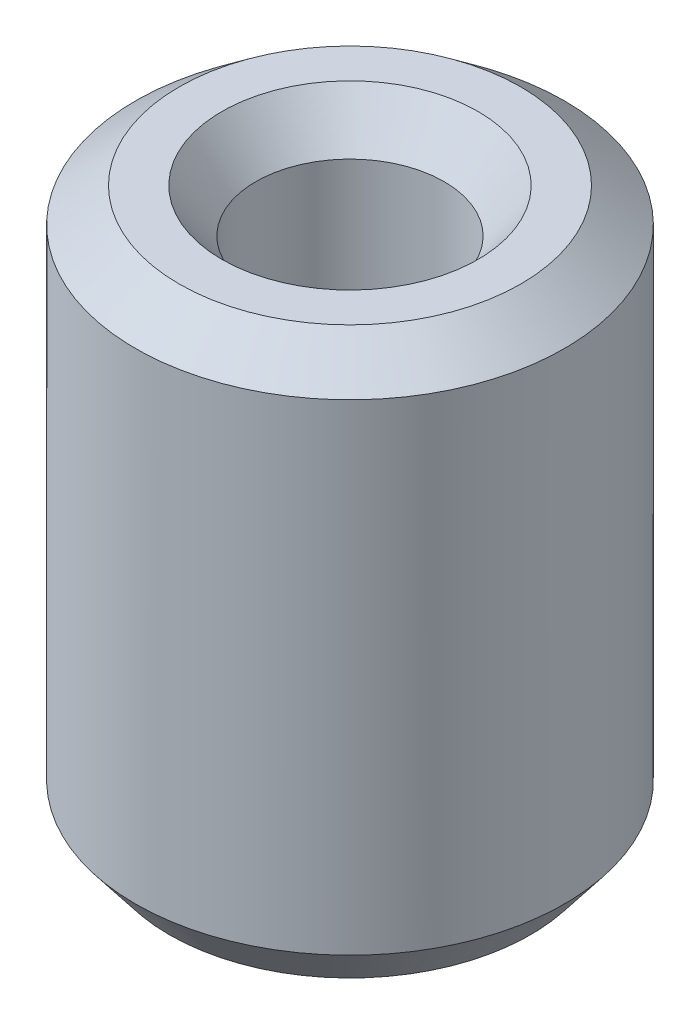
SolidWorks part; units mm, degrees
ref_plane "Front Plane" through (0, 0, 0) normal (0, 0, 1) x (1, 0, 0)
ref_plane "Top Plane" through (0, 0, 0) normal (0, 1, 0) x (1, 0, 0)
ref_plane "Right Plane" through (0, 0, 0) normal (1, 0, 0) x (0, 0, -1)
sketch "Sketch1" plane through (0, 0, 0) normal (0, 1, 0) x (1, 0, 0)
  circle A0 centre (0, 0) radius 20
  dimension "SLEEVE_OD" = 40
extrude "Boss-Extrude1" add sketch "Sketch1" along normal blind 52.093
sketch "Sketch2" plane through (0, 0, 0) normal (0, 1, 0) x (1, 0, 0)
  circle A0 centre (0, 0) radius 8.7797
  dimension "BORE_D" = 17.5593
extrude "Cut-Extrude1" cut sketch "Sketch2" along normal through all
chamfer "Chamfer1" distance 3.167 angle 52.162 4 edges at (0, 52.093, 8.7797) (0, 0, 8.7797) (0, 0, 20) (0, 52.093, 20) first distance on face at (0, 52.093, 8.7797) first distance on face at (0, 0, 8.7797) first distance on face at (0, 52.093, 20)
